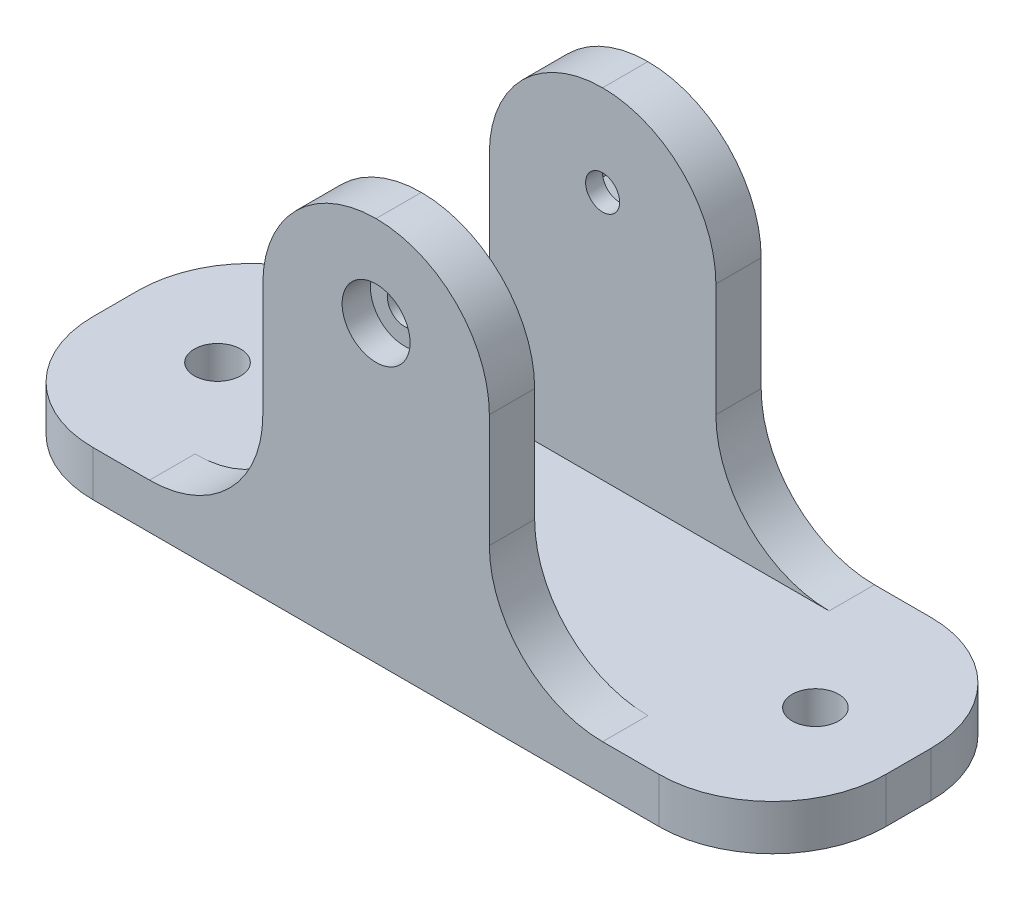
SolidWorks part; units mm, degrees
ref_plane "Front Plane" through (0, 0, 0) normal (0, 0, 1) x (1, 0, 0)
ref_plane "Top Plane" through (0, 0, 0) normal (0, 1, 0) x (1, 0, 0)
ref_plane "Right Plane" through (0, 0, 0) normal (1, 0, 0) x (0, 0, -1)
sketch "Sketch1" plane through (0, 0, 0) normal (0, 1, 0) x (1, 0, 0)
  line L1 (-35, -12) -> (35, -12)
  line L2 (-35, -12) -> (-35, 12)
  line L3 (-35, 12) -> (35, 12)
  line L4 (35, -12) -> (35, 12)
  line L5 (-35, -12) -> (35, 12) construction
  line L6 (-35, 12) -> (35, -12) construction
  point P0 (0, 0)
  dimension "D1" = 70
  dimension "D2" = 24
extrude "Boss-Extrude1" add sketch "Sketch1" along normal mid plane 4
sketch "Sketch2" plane through (0, 2, 0) normal (0, 1, 0) x (1, 0, 0)
  line L0 (35, 12) -> (-35, 12) construction
  line L5 (-10, 12) -> (10, 12)
  line L6 (-10, 12) -> (-10, 8)
  line L7 (-10, 8) -> (10, 8)
  line L8 (10, 12) -> (10, 8)
  line L9 (0, 0) -> (4.1292, 0) construction
  line L10 (-10, -8) -> (10, -8)
  line L11 (10, -12) -> (10, -8)
  line L12 (-10, -12) -> (10, -12)
  line L13 (-10, -12) -> (-10, -8)
  point P6 (0, 8)
  dimension "D1" = 4
  dimension "D2" = 20
extrude "Boss-Extrude2" add sketch "Sketch2" along normal blind 30
fillet "Fillet1" radius 10 4 edges at (-10, 2, -10) (-10, 2, 10) (10, 2, -10) (10, 2, 10)
fillet "Fillet2" radius 10 4 edges at (-10, 32, 10) (10, 32, 10) (10, 32, -10) (-10, 32, -10)
sketch "Sketch3" plane through (0, 0, 12) normal (0, 0, 1) x (1, 0, 0)
  circle A0 centre (0, 24) radius 1.5
  dimension "D1" = 3
  dimension "D2" = 8
extrude "Cut-Extrude1" cut sketch "Sketch3" against normal up to surface (24 mm away) contours A0 up to face at (0, 9.4545, -12)
fillet "Fillet3" radius 10 4 edges at (35, 0, 12) (35, 0, -12) (-35, 0, -12) (-35, 0, 12)
sketch "Sketch4" plane through (0, 2, 0) normal (0, 1, 0) x (1, 0, 0)
  line L0 (-35, 2) -> (-35, -2) construction
  circle A0 centre (-26, 0) radius 2.05
  circle A1 centre (26.7892, 0) radius 2.05
  dimension "D1" = 4.1
  dimension "D2" = 9
extrude "Cut-Extrude2" cut sketch "Sketch4" against normal up to surface (4 mm away) up to face at (0, -2, 0)
sketch "Sketch5" plane through (0, 0, 12) normal (0, 0, 1) x (1, 0, 0)
  circle A0 centre (0, 24) radius 3
  dimension "D1" = 6
extrude "Cut-Extrude3" cut sketch "Sketch5" against normal blind 2.5
sketch "Sketch6" plane through (0, 0, -12) normal (0, 0, -1) x (-1, 0, 0)
  line L1 (2.75, 25.5877) -> (0, 27.1754)
  line L2 (0, 27.1754) -> (-2.75, 25.5877)
  line L3 (-2.75, 25.5877) -> (-2.75, 22.4123)
  line L4 (-2.75, 22.4123) -> (0, 20.8246)
  line L5 (0, 20.8246) -> (2.75, 22.4123)
  line L6 (2.75, 22.4123) -> (2.75, 25.5877)
  circle A0 centre (0, 24) radius 2.75 construction
  dimension "D1" = 5.5
extrude "Cut-Extrude4" cut sketch "Sketch6" against normal blind 2.5
